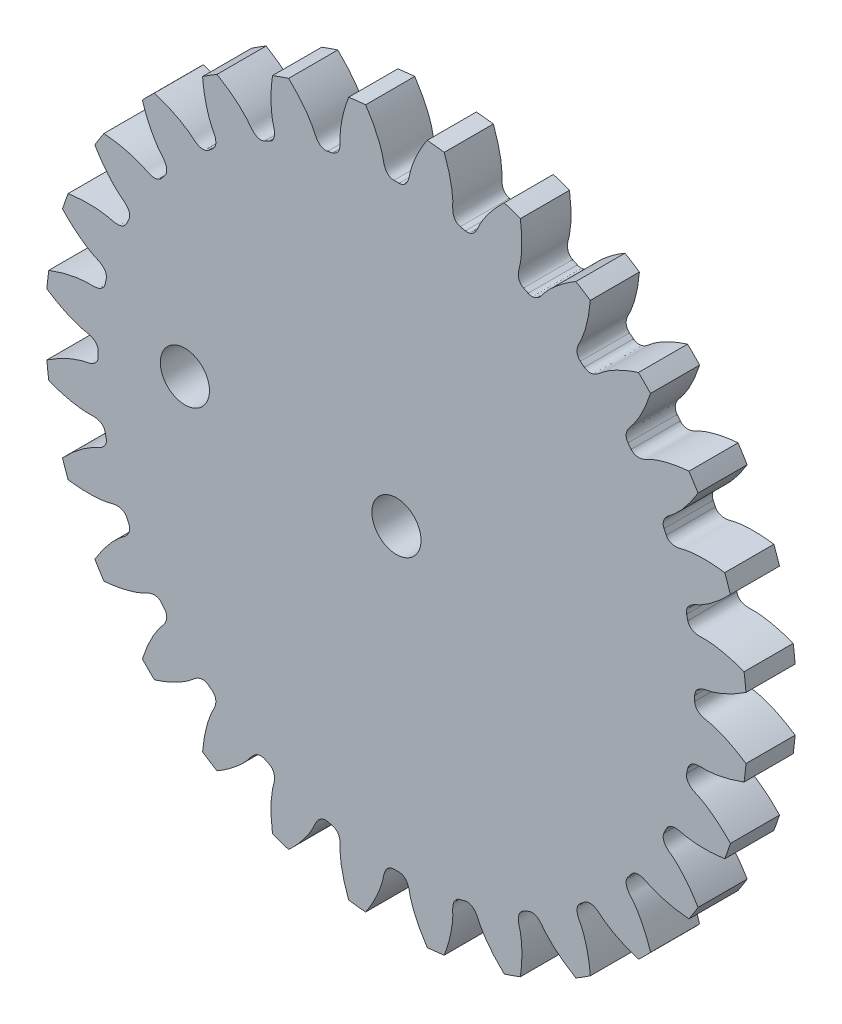
SolidWorks part; units mm, degrees
ref_plane "Front Plane" through (0, 0, 0) normal (0, 0, 1) x (1, 0, 0)
ref_plane "Top Plane" through (0, 0, 0) normal (0, 1, 0) x (1, 0, 0)
ref_plane "Right Plane" through (0, 0, 0) normal (1, 0, 0) x (0, 0, -1)
ref_axis "Axis1" through (0, 0, -88.99) along (0, 0, 1)
sketch "Gear-BaseSketch" plane through (0, 0, 0) normal (0, 0, 1) x (1, 0, 0)
  circle A0 centre (0, 0) radius 21.4286
  dimension "D1" = 42.8571
extrude "Company Standard #1, 40.0000mm P.D." add sketch "Gear-BaseSketch" along normal mid plane 3
sketch "Tooth-Sketch; Backlash: 0.0000mm" plane through (0, 0, 0) normal (0, 0, 1) x (1, 0, 0)
  line L0 (0, 0) -> (0, 28.1908) construction
  arc A0 (-1.9415, 21.4374) -> (1.9415, 21.4374) centre (0, 0) cw
  arc A1 (-0.1566, 18.2136) -> (0.1566, 18.2136) centre (0, 0) cw
  spline S0 degree 3 poles (-1.9415, 21.4374) (-1.8044, 21.2368) (-1.616, 20.9396) (-1.3966, 20.545) (-1.261, 20.2779) (-1.1462, 20.0297) (-1.0508, 19.8014) (-0.9731, 19.5941) (-0.9113, 19.4087) (-0.8638, 19.2462) (-0.8287, 19.1073) (-0.8066, 19.0043) (-0.7939, 18.9333) (-0.7853, 18.8868) (-0.7763, 18.8451) (-0.7601, 18.7782) (-0.7329, 18.6876) (-0.6861, 18.5751) (-0.6225, 18.4654) (-0.5313, 18.3572) (-0.3805, 18.2476) (-0.2408, 18.214) (-0.1566, 18.2136) knots 0 0 0 0 0.190812 0.275995 0.354364 0.425919 0.490658 0.548583 0.599694 0.643989 0.68147 0.712136 0.726696 0.738084 0.749246 0.760205 0.792121 0.82341 0.855639 0.891318 0.933791 1 1 1 1
  spline S1 degree 3 poles (1.9415, 21.4374) (1.8044, 21.2368) (1.616, 20.9396) (1.3966, 20.545) (1.261, 20.2779) (1.1462, 20.0297) (1.0508, 19.8014) (0.9731, 19.5941) (0.9113, 19.4087) (0.8638, 19.2462) (0.8287, 19.1073) (0.8066, 19.0043) (0.7939, 18.9333) (0.7853, 18.8868) (0.7763, 18.8451) (0.7601, 18.7782) (0.7329, 18.6876) (0.6861, 18.5751) (0.6225, 18.4654) (0.5313, 18.3572) (0.3805, 18.2476) (0.2408, 18.214) (0.1566, 18.2136) knots 0 0 0 0 0.190812 0.275995 0.354364 0.425919 0.490658 0.548583 0.599694 0.643989 0.68147 0.712136 0.726696 0.738084 0.749246 0.760205 0.792121 0.82341 0.855639 0.891318 0.933791 1 1 1 1
extrude "Tooth-Cut, D.P.=17.7800, P.A.=20.000deg" cut sketch "Tooth-Sketch; Backlash: 0.0000mm" against normal through all and the other way through all
pattern_circular "Tooth Pattern, 28 / 28" count 28 every 12.857 about axis through (0, 0, -88.99) along (0, 0, 1) of "Tooth-Cut, D.P.=17.7800, P.A.=20.000deg"
sketch "Sketch1" plane through (0, 0, 1.5) normal (0, 0, 1) x (1, 0, 0)
  line L0 (0, 0) -> (-21.2938, 2.3992) construction
  circle A0 centre (0, 0) radius 1.5
  circle A1 centre (-12.9183, 1.4555) radius 1.5
  arc A3 (-21.2291, 2.9173) -> (-21.346, 1.8797) centre (0, 0) ccw construction
  dimension "D1" = 3
  dimension "D2" = 13
extrude "Cut-Extrude2" cut sketch "Sketch1" against normal through all
